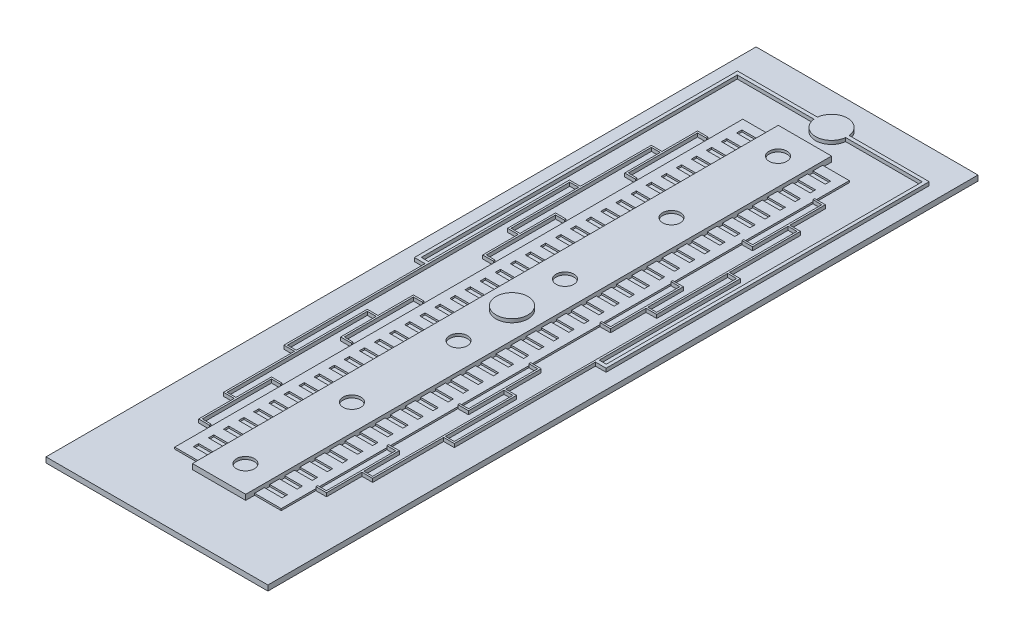
SolidWorks part; units mm, degrees
ref_plane "Front Plane" through (0, 0, 0) normal (0, 0, 1) x (1, 0, 0)
ref_plane "Top Plane" through (0, 0, 0) normal (0, 1, 0) x (1, 0, 0)
ref_plane "Right Plane" through (0, 0, 0) normal (1, 0, 0) x (0, 0, -1)
sketch "Sketch2" plane through (0, 0, 0) normal (0, 1, 0) x (1, 0, 0)
  line L1 (-6.25, 20) -> (6.25, 20)
  line L2 (-6.25, 20) -> (-6.25, -20)
  line L3 (-6.25, -20) -> (6.25, -20)
  line L4 (6.25, 20) -> (6.25, -20)
  line L5 (-6.25, 20) -> (6.25, -20) construction
  line L6 (-6.25, -20) -> (6.25, 20) construction
  point P0 (0, 0)
extrude "Boss-Extrude1" add sketch "Sketch2" along normal blind 0.3
sketch "Sketch3" plane through (0, 0.3, 0) normal (0, 1, 0) x (1, 0, 0)
  line L1 (-1.5, 16.5) -> (1.5, 16.5)
  line L2 (-1.5, 16.5) -> (-1.5, -16.5)
  line L3 (-1.5, -16.5) -> (1.5, -16.5)
  line L4 (1.5, 16.5) -> (1.5, -16.5)
  line L5 (-1.5, 16.5) -> (1.5, -16.5) construction
  line L6 (-1.5, -16.5) -> (1.5, 16.5) construction
  point P0 (0, 0)
extrude "Boss-Extrude2" add sketch "Sketch3" along normal blind 0.3
sketch "Sketch4" plane through (0, 0.3, 0) normal (0, 1, 0) x (1, 0, 0)
  line L0 (1.5, 16) -> (3, 16)
  line L1 (1.5, 16) -> (1.5, -16)
  line L2 (3, 16) -> (3, -16)
  line L3 (1.5, -16) -> (3, -16)
  line L4 (1.5, -16.5) -> (1.5, 16.5) construction
  line L5 (0, 18.1281) -> (0, -18.1281) construction
  line L6 (-3, 16) -> (-3, -16)
  line L7 (-1.5, -16) -> (-3, -16)
  line L8 (-1.5, 16) -> (-1.5, -16)
  line L9 (-1.5, 16) -> (-3, 16)
  point P11 (0, 0)
  dimension "D1" = 0.5
extrude "Boss-Extrude3" add sketch "Sketch4" along normal blind 0.1
sketch "Sketch5" plane through (0, 0.4, 0) normal (0, 1, 0) x (1, 0, 0)
  line L0 (1.5, 15.45) -> (2.5, 15.45)
  line L1 (1.5, 15.45) -> (1.5, 15.15)
  line L2 (2.5, 15.45) -> (2.5, 15.15)
  line L3 (1.5, 15.15) -> (2.5, 15.15)
  line L4 (1.5, -16.5) -> (1.5, 16.5) construction
  line L5 (-2.5, 15.45) -> (-1.5, 15.45)
  line L6 (-2.5, 15.45) -> (-2.5, 15.15)
  line L7 (-2.5, 15.15) -> (-1.5, 15.15)
  line L8 (-1.5, 15.45) -> (-1.5, 15.15)
  line L9 (-2.5, 14.6) -> (-1.5, 14.6)
  line L10 (-2.5, 14.6) -> (-2.5, 14.3)
  line L11 (-2.5, 14.3) -> (-1.5, 14.3)
  line L12 (-1.5, 14.6) -> (-1.5, 14.3)
  line L13 (-2.5, 13.75) -> (-1.5, 13.75)
  line L14 (-2.5, 13.75) -> (-2.5, 13.45)
  line L15 (-2.5, 13.45) -> (-1.5, 13.45)
  line L16 (-1.5, 13.75) -> (-1.5, 13.45)
  line L17 (-2.5, 12.9) -> (-1.5, 12.9)
  line L18 (-2.5, 12.9) -> (-2.5, 12.6)
  line L19 (-2.5, 12.6) -> (-1.5, 12.6)
  line L20 (-1.5, 12.9) -> (-1.5, 12.6)
  line L21 (-2.5, 12.05) -> (-1.5, 12.05)
  line L22 (-2.5, 12.05) -> (-2.5, 11.75)
  line L23 (-2.5, 11.75) -> (-1.5, 11.75)
  line L24 (-1.5, 12.05) -> (-1.5, 11.75)
  line L25 (-2.5, 11.2) -> (-1.5, 11.2)
  line L26 (-2.5, 11.2) -> (-2.5, 10.9)
  line L27 (-2.5, 10.9) -> (-1.5, 10.9)
  line L28 (-1.5, 11.2) -> (-1.5, 10.9)
  line L29 (-2.5, 10.35) -> (-1.5, 10.35)
  line L30 (-2.5, 10.35) -> (-2.5, 10.05)
  line L31 (-2.5, 10.05) -> (-1.5, 10.05)
  line L32 (-1.5, 10.35) -> (-1.5, 10.05)
  line L33 (-2.5, 9.5) -> (-1.5, 9.5)
  line L34 (-2.5, 9.5) -> (-2.5, 9.2)
  line L35 (-2.5, 9.2) -> (-1.5, 9.2)
  line L36 (-1.5, 9.5) -> (-1.5, 9.2)
  line L37 (-2.5, 8.65) -> (-1.5, 8.65)
  line L38 (-2.5, 8.65) -> (-2.5, 8.35)
  line L39 (-2.5, 8.35) -> (-1.5, 8.35)
  line L40 (-1.5, 8.65) -> (-1.5, 8.35)
  line L41 (-2.5, 7.8) -> (-1.5, 7.8)
  line L42 (-2.5, 7.8) -> (-2.5, 7.5)
  line L43 (-2.5, 7.5) -> (-1.5, 7.5)
  line L44 (-1.5, 7.8) -> (-1.5, 7.5)
  line L45 (-2.5, 6.95) -> (-1.5, 6.95)
  line L46 (-2.5, 6.95) -> (-2.5, 6.65)
  line L47 (-2.5, 6.65) -> (-1.5, 6.65)
  line L48 (-1.5, 6.95) -> (-1.5, 6.65)
  line L49 (-2.5, 6.1) -> (-1.5, 6.1)
  line L50 (-2.5, 6.1) -> (-2.5, 5.8)
  line L51 (-2.5, 5.8) -> (-1.5, 5.8)
  line L52 (-1.5, 6.1) -> (-1.5, 5.8)
  line L53 (-2.5, 5.25) -> (-1.5, 5.25)
  line L54 (-2.5, 5.25) -> (-2.5, 4.95)
  line L55 (-2.5, 4.95) -> (-1.5, 4.95)
  line L56 (-1.5, 5.25) -> (-1.5, 4.95)
  line L57 (-2.5, 4.4) -> (-1.5, 4.4)
  line L58 (-2.5, 4.4) -> (-2.5, 4.1)
  line L59 (-2.5, 4.1) -> (-1.5, 4.1)
  line L60 (-1.5, 4.4) -> (-1.5, 4.1)
  line L61 (-2.5, 3.55) -> (-1.5, 3.55)
  line L62 (-2.5, 3.55) -> (-2.5, 3.25)
  line L63 (-2.5, 3.25) -> (-1.5, 3.25)
  line L64 (-1.5, 3.55) -> (-1.5, 3.25)
  line L65 (-2.5, 2.7) -> (-1.5, 2.7)
  line L66 (-2.5, 2.7) -> (-2.5, 2.4)
  line L67 (-2.5, 2.4) -> (-1.5, 2.4)
  line L68 (-1.5, 2.7) -> (-1.5, 2.4)
  line L69 (-2.5, 1.85) -> (-1.5, 1.85)
  line L70 (-2.5, 1.85) -> (-2.5, 1.55)
  line L71 (-2.5, 1.55) -> (-1.5, 1.55)
  line L72 (-1.5, 1.85) -> (-1.5, 1.55)
  line L73 (-2.5, 1) -> (-1.5, 1)
  line L74 (-2.5, 1) -> (-2.5, 0.7)
  line L75 (-2.5, 0.7) -> (-1.5, 0.7)
  line L76 (-1.5, 1) -> (-1.5, 0.7)
  line L77 (-2.5, 0.15) -> (-1.5, 0.15)
  line L78 (-2.5, 0.15) -> (-2.5, -0.15)
  line L79 (-2.5, -0.15) -> (-1.5, -0.15)
  line L80 (-1.5, 0.15) -> (-1.5, -0.15)
  line L81 (-2.5, -0.7) -> (-1.5, -0.7)
  line L82 (-2.5, -0.7) -> (-2.5, -1)
  line L83 (-2.5, -1) -> (-1.5, -1)
  line L84 (-1.5, -0.7) -> (-1.5, -1)
  line L85 (-2.5, -1.55) -> (-1.5, -1.55)
  line L86 (-2.5, -1.55) -> (-2.5, -1.85)
  line L87 (-2.5, -1.85) -> (-1.5, -1.85)
  line L88 (-1.5, -1.55) -> (-1.5, -1.85)
  line L89 (-2.5, -2.4) -> (-1.5, -2.4)
  line L90 (-2.5, -2.4) -> (-2.5, -2.7)
  line L91 (-2.5, -2.7) -> (-1.5, -2.7)
  line L92 (-1.5, -2.4) -> (-1.5, -2.7)
  line L93 (-2.5, -3.25) -> (-1.5, -3.25)
  line L94 (-2.5, -3.25) -> (-2.5, -3.55)
  line L95 (-2.5, -3.55) -> (-1.5, -3.55)
  line L96 (-1.5, -3.25) -> (-1.5, -3.55)
  line L97 (-2.5, -4.1) -> (-1.5, -4.1)
  line L98 (-2.5, -4.1) -> (-2.5, -4.4)
  line L99 (-2.5, -4.4) -> (-1.5, -4.4)
  line L100 (-1.5, -4.1) -> (-1.5, -4.4)
  line L101 (-2.5, -4.95) -> (-1.5, -4.95)
  line L102 (-2.5, -4.95) -> (-2.5, -5.25)
  line L103 (-2.5, -5.25) -> (-1.5, -5.25)
  line L104 (-1.5, -4.95) -> (-1.5, -5.25)
  line L105 (-2.5, -5.8) -> (-1.5, -5.8)
  line L106 (-2.5, -5.8) -> (-2.5, -6.1)
  line L107 (-2.5, -6.1) -> (-1.5, -6.1)
  line L108 (-1.5, -5.8) -> (-1.5, -6.1)
  line L109 (-2.5, -6.65) -> (-1.5, -6.65)
  line L110 (-2.5, -6.65) -> (-2.5, -6.95)
  line L111 (-2.5, -6.95) -> (-1.5, -6.95)
  line L112 (-1.5, -6.65) -> (-1.5, -6.95)
  line L113 (-2.5, -7.5) -> (-1.5, -7.5)
  line L114 (-2.5, -7.5) -> (-2.5, -7.8)
  line L115 (-2.5, -7.8) -> (-1.5, -7.8)
  line L116 (-1.5, -7.5) -> (-1.5, -7.8)
  line L117 (-2.5, -8.35) -> (-1.5, -8.35)
  line L118 (-2.5, -8.35) -> (-2.5, -8.65)
  line L119 (-2.5, -8.65) -> (-1.5, -8.65)
  line L120 (-1.5, -8.35) -> (-1.5, -8.65)
  line L121 (-2.5, -9.2) -> (-1.5, -9.2)
  line L122 (-2.5, -9.2) -> (-2.5, -9.5)
  line L123 (-2.5, -9.5) -> (-1.5, -9.5)
  line L124 (-1.5, -9.2) -> (-1.5, -9.5)
  line L125 (-2.5, -10.05) -> (-1.5, -10.05)
  line L126 (-2.5, -10.05) -> (-2.5, -10.35)
  line L127 (-2.5, -10.35) -> (-1.5, -10.35)
  line L128 (-1.5, -10.05) -> (-1.5, -10.35)
  line L129 (-2.5, -10.9) -> (-1.5, -10.9)
  line L130 (-2.5, -10.9) -> (-2.5, -11.2)
  line L131 (-2.5, -11.2) -> (-1.5, -11.2)
  line L132 (-1.5, -10.9) -> (-1.5, -11.2)
  line L133 (-2.5, -11.75) -> (-1.5, -11.75)
  line L134 (-2.5, -11.75) -> (-2.5, -12.05)
  line L135 (-2.5, -12.05) -> (-1.5, -12.05)
  line L136 (-1.5, -11.75) -> (-1.5, -12.05)
  line L137 (-2.5, -12.6) -> (-1.5, -12.6)
  line L138 (-2.5, -12.6) -> (-2.5, -12.9)
  line L139 (-2.5, -12.9) -> (-1.5, -12.9)
  line L140 (-1.5, -12.6) -> (-1.5, -12.9)
  line L141 (-2.5, -13.45) -> (-1.5, -13.45)
  line L142 (-2.5, -13.45) -> (-2.5, -13.75)
  line L143 (-2.5, -13.75) -> (-1.5, -13.75)
  line L144 (-1.5, -13.45) -> (-1.5, -13.75)
  line L145 (-2.5, -14.3) -> (-1.5, -14.3)
  line L146 (-2.5, -14.3) -> (-2.5, -14.6)
  line L147 (-2.5, -14.6) -> (-1.5, -14.6)
  line L148 (-1.5, -14.3) -> (-1.5, -14.6)
  line L149 (-2.5, -15.15) -> (-1.5, -15.15)
  line L150 (-2.5, -15.15) -> (-2.5, -15.45)
  line L151 (-2.5, -15.45) -> (-1.5, -15.45)
  line L152 (-1.5, -15.15) -> (-1.5, -15.45)
  line L153 (1.5, 14.6) -> (2.5, 14.6)
  line L154 (1.5, 14.6) -> (1.5, 14.3)
  line L155 (1.5, 14.3) -> (2.5, 14.3)
  line L156 (2.5, 14.6) -> (2.5, 14.3)
  line L157 (1.5, 13.75) -> (2.5, 13.75)
  line L158 (1.5, 13.75) -> (1.5, 13.45)
  line L159 (1.5, 13.45) -> (2.5, 13.45)
  line L160 (2.5, 13.75) -> (2.5, 13.45)
  line L161 (1.5, 12.9) -> (2.5, 12.9)
  line L162 (1.5, 12.9) -> (1.5, 12.6)
  line L163 (1.5, 12.6) -> (2.5, 12.6)
  line L164 (2.5, 12.9) -> (2.5, 12.6)
  line L165 (1.5, 12.05) -> (2.5, 12.05)
  line L166 (1.5, 12.05) -> (1.5, 11.75)
  line L167 (1.5, 11.75) -> (2.5, 11.75)
  line L168 (2.5, 12.05) -> (2.5, 11.75)
  line L169 (1.5, 11.2) -> (2.5, 11.2)
  line L170 (1.5, 11.2) -> (1.5, 10.9)
  line L171 (1.5, 10.9) -> (2.5, 10.9)
  line L172 (2.5, 11.2) -> (2.5, 10.9)
  line L173 (1.5, 10.35) -> (2.5, 10.35)
  line L174 (1.5, 10.35) -> (1.5, 10.05)
  line L175 (1.5, 10.05) -> (2.5, 10.05)
  line L176 (2.5, 10.35) -> (2.5, 10.05)
  line L177 (1.5, 9.5) -> (2.5, 9.5)
  line L178 (1.5, 9.5) -> (1.5, 9.2)
  line L179 (1.5, 9.2) -> (2.5, 9.2)
  line L180 (2.5, 9.5) -> (2.5, 9.2)
  line L181 (1.5, 8.65) -> (2.5, 8.65)
  line L182 (1.5, 8.65) -> (1.5, 8.35)
  line L183 (1.5, 8.35) -> (2.5, 8.35)
  line L184 (2.5, 8.65) -> (2.5, 8.35)
  line L185 (1.5, 7.8) -> (2.5, 7.8)
  line L186 (1.5, 7.8) -> (1.5, 7.5)
  line L187 (1.5, 7.5) -> (2.5, 7.5)
  line L188 (2.5, 7.8) -> (2.5, 7.5)
  line L189 (1.5, 6.95) -> (2.5, 6.95)
  line L190 (1.5, 6.95) -> (1.5, 6.65)
  line L191 (1.5, 6.65) -> (2.5, 6.65)
  line L192 (2.5, 6.95) -> (2.5, 6.65)
  line L193 (1.5, 6.1) -> (2.5, 6.1)
  line L194 (1.5, 6.1) -> (1.5, 5.8)
  line L195 (1.5, 5.8) -> (2.5, 5.8)
  line L196 (2.5, 6.1) -> (2.5, 5.8)
  line L197 (1.5, 5.25) -> (2.5, 5.25)
  line L198 (1.5, 5.25) -> (1.5, 4.95)
  line L199 (1.5, 4.95) -> (2.5, 4.95)
  line L200 (2.5, 5.25) -> (2.5, 4.95)
  line L201 (1.5, 4.4) -> (2.5, 4.4)
  line L202 (1.5, 4.4) -> (1.5, 4.1)
  line L203 (1.5, 4.1) -> (2.5, 4.1)
  line L204 (2.5, 4.4) -> (2.5, 4.1)
  line L205 (1.5, 3.55) -> (2.5, 3.55)
  line L206 (1.5, 3.55) -> (1.5, 3.25)
  line L207 (1.5, 3.25) -> (2.5, 3.25)
  line L208 (2.5, 3.55) -> (2.5, 3.25)
  line L209 (1.5, 2.7) -> (2.5, 2.7)
  line L210 (1.5, 2.7) -> (1.5, 2.4)
  line L211 (1.5, 2.4) -> (2.5, 2.4)
  line L212 (2.5, 2.7) -> (2.5, 2.4)
  line L213 (1.5, 1.85) -> (2.5, 1.85)
  line L214 (1.5, 1.85) -> (1.5, 1.55)
  line L215 (1.5, 1.55) -> (2.5, 1.55)
  line L216 (2.5, 1.85) -> (2.5, 1.55)
  line L217 (1.5, 1) -> (2.5, 1)
  line L218 (1.5, 1) -> (1.5, 0.7)
  line L219 (1.5, 0.7) -> (2.5, 0.7)
  line L220 (2.5, 1) -> (2.5, 0.7)
  line L221 (1.5, 0.15) -> (2.5, 0.15)
  line L222 (1.5, 0.15) -> (1.5, -0.15)
  line L223 (1.5, -0.15) -> (2.5, -0.15)
  line L224 (2.5, 0.15) -> (2.5, -0.15)
  line L225 (1.5, -0.7) -> (2.5, -0.7)
  line L226 (1.5, -0.7) -> (1.5, -1)
  line L227 (1.5, -1) -> (2.5, -1)
  line L228 (2.5, -0.7) -> (2.5, -1)
  line L229 (1.5, -1.55) -> (2.5, -1.55)
  line L230 (1.5, -1.55) -> (1.5, -1.85)
  line L231 (1.5, -1.85) -> (2.5, -1.85)
  line L232 (2.5, -1.55) -> (2.5, -1.85)
  line L233 (1.5, -2.4) -> (2.5, -2.4)
  line L234 (1.5, -2.4) -> (1.5, -2.7)
  line L235 (1.5, -2.7) -> (2.5, -2.7)
  line L236 (2.5, -2.4) -> (2.5, -2.7)
  line L237 (1.5, -3.25) -> (2.5, -3.25)
  line L238 (1.5, -3.25) -> (1.5, -3.55)
  line L239 (1.5, -3.55) -> (2.5, -3.55)
  line L240 (2.5, -3.25) -> (2.5, -3.55)
  line L241 (1.5, -4.1) -> (2.5, -4.1)
  line L242 (1.5, -4.1) -> (1.5, -4.4)
  line L243 (1.5, -4.4) -> (2.5, -4.4)
  line L244 (2.5, -4.1) -> (2.5, -4.4)
  line L245 (1.5, -4.95) -> (2.5, -4.95)
  line L246 (1.5, -4.95) -> (1.5, -5.25)
  line L247 (1.5, -5.25) -> (2.5, -5.25)
  line L248 (2.5, -4.95) -> (2.5, -5.25)
  line L249 (1.5, -5.8) -> (2.5, -5.8)
  line L250 (1.5, -5.8) -> (1.5, -6.1)
  line L251 (1.5, -6.1) -> (2.5, -6.1)
  line L252 (2.5, -5.8) -> (2.5, -6.1)
  line L253 (1.5, -6.65) -> (2.5, -6.65)
  line L254 (1.5, -6.65) -> (1.5, -6.95)
  line L255 (1.5, -6.95) -> (2.5, -6.95)
  line L256 (2.5, -6.65) -> (2.5, -6.95)
  line L257 (1.5, -7.5) -> (2.5, -7.5)
  line L258 (1.5, -7.5) -> (1.5, -7.8)
  line L259 (1.5, -7.8) -> (2.5, -7.8)
  line L260 (2.5, -7.5) -> (2.5, -7.8)
  line L261 (1.5, -8.35) -> (2.5, -8.35)
  line L262 (1.5, -8.35) -> (1.5, -8.65)
  line L263 (1.5, -8.65) -> (2.5, -8.65)
  line L264 (2.5, -8.35) -> (2.5, -8.65)
  line L265 (1.5, -9.2) -> (2.5, -9.2)
  line L266 (1.5, -9.2) -> (1.5, -9.5)
  line L267 (1.5, -9.5) -> (2.5, -9.5)
  line L268 (2.5, -9.2) -> (2.5, -9.5)
  line L269 (1.5, -10.05) -> (2.5, -10.05)
  line L270 (1.5, -10.05) -> (1.5, -10.35)
  line L271 (1.5, -10.35) -> (2.5, -10.35)
  line L272 (2.5, -10.05) -> (2.5, -10.35)
  line L273 (1.5, -10.9) -> (2.5, -10.9)
  line L274 (1.5, -10.9) -> (1.5, -11.2)
  line L275 (1.5, -11.2) -> (2.5, -11.2)
  line L276 (2.5, -10.9) -> (2.5, -11.2)
  line L277 (1.5, -11.75) -> (2.5, -11.75)
  line L278 (1.5, -11.75) -> (1.5, -12.05)
  line L279 (1.5, -12.05) -> (2.5, -12.05)
  line L280 (2.5, -11.75) -> (2.5, -12.05)
  line L281 (1.5, -12.6) -> (2.5, -12.6)
  line L282 (1.5, -12.6) -> (1.5, -12.9)
  line L283 (1.5, -12.9) -> (2.5, -12.9)
  line L284 (2.5, -12.6) -> (2.5, -12.9)
  line L285 (1.5, -13.45) -> (2.5, -13.45)
  line L286 (1.5, -13.45) -> (1.5, -13.75)
  line L287 (1.5, -13.75) -> (2.5, -13.75)
  line L288 (2.5, -13.45) -> (2.5, -13.75)
  line L289 (1.5, -14.3) -> (2.5, -14.3)
  line L290 (1.5, -14.3) -> (1.5, -14.6)
  line L291 (1.5, -14.6) -> (2.5, -14.6)
  line L292 (2.5, -14.3) -> (2.5, -14.6)
  line L293 (1.5, -15.15) -> (2.5, -15.15)
  line L294 (1.5, -15.15) -> (1.5, -15.45)
  line L295 (1.5, -15.45) -> (2.5, -15.45)
  line L296 (2.5, -15.15) -> (2.5, -15.45)
  dimension "D1" = 0.55
  dimension "D2" = 2
  dimension "D3" = 37
extrude "Cut-Extrude1" cut sketch "Sketch5" against normal blind 0.1
sketch "Sketch6" plane through (0, 0.3, 0) normal (0, 1, 0) x (1, 0, 0)
  line L0 (-11.4943, 0) -> (11.4943, 0) construction
  line L1 (0, 19.3574) -> (0, -19.3574) construction
  line L2 (1.5, 16.5) -> (-1.5, 16.5) construction
  line L3 (-5.4, 18.1) -> (5.4, 18.1)
  line L4 (-5.2112, 17.9) -> (5.2112, 17.9)
  line L5 (-5.4, 18.1) -> (-5.4, -0.1)
  line L6 (-5.2112, 17.9) -> (-5.2112, 0.1)
  line L7 (-5.2112, 0.1) -> (-4.8112, 0.1)
  line L8 (-5.4, -0.1) -> (-4.8, -0.1)
  line L9 (-3, 16) -> (-3, -16) construction
  line L10 (-3, 16) -> (-3, -16) construction
  line L11 (-3, 14.05) -> (-3.6, 14.05)
  line L12 (-3, 13.95) -> (-3.5, 13.95)
  line L13 (-3, 9.95) -> (-3.6, 9.95)
  line L14 (-3, 10.05) -> (-3.5, 10.05)
  line L15 (-3.5, 10.05) -> (-3.5, 13.95)
  line L16 (-3.6, 14.05) -> (-3.6, 12.05)
  line L17 (-3.6, 11.95) -> (-3.6, 9.95)
  line L18 (-3, 12) -> (-3.7147, 12) construction
  line L19 (-3, 6.05) -> (-3.6, 6.05)
  line L20 (-3, 5.95) -> (-3.5, 5.95)
  line L21 (-3, 1.95) -> (-3.6, 1.95)
  line L22 (-3, 2.05) -> (-3.5, 2.05)
  line L23 (-3.5, 2.05) -> (-3.5, 5.95)
  line L24 (-3.6, 6.05) -> (-3.6, 4.05)
  line L25 (-3.6, 3.95) -> (-3.6, 1.95)
  line L26 (-3, -1.95) -> (-3.6, -1.9555)
  line L27 (-3, -2.05) -> (-3.5, -2.0545)
  line L28 (-3, -6.05) -> (-3.6, -6.05)
  line L29 (-3, -5.95) -> (-3.5, -5.95)
  line L30 (-3.5, -5.95) -> (-3.5, -2.0545)
  line L31 (-3.6, -1.9555) -> (-3.6, -3.95)
  line L32 (-3.6, -4.05) -> (-3.6, -6.05)
  line L33 (-3, -9.95) -> (-3.6, -9.95)
  line L34 (-3, -10.05) -> (-3.5, -10.05)
  line L35 (-3, -14.05) -> (-3.6, -14.05)
  line L36 (-3, -13.95) -> (-3.5, -13.95)
  line L37 (-3.5, -13.95) -> (-3.5, -10.05)
  line L38 (-3.6, -9.95) -> (-3.6, -11.95)
  line L39 (-3.6, -12.05) -> (-3.6, -14.05)
  line L40 (-3, 4) -> (-3.6713, 4) construction
  line L41 (-3, -4) -> (-3.7566, -4) construction
  line L42 (-3, -12) -> (-3.7566, -12) construction
  line L43 (-3.6, 12.05) -> (-4.2, 12.05)
  line L44 (-3.6, 11.95) -> (-4.1, 11.95)
  line L45 (-3.6, 3.95) -> (-4.2, 3.95)
  line L46 (-3.6, 4.05) -> (-4.1, 4.05)
  line L47 (-4.1, 4.05) -> (-4.1, 11.95)
  line L48 (-4.2, 12.05) -> (-4.2, 8.05)
  line L49 (-4.2, 7.95) -> (-4.2, 3.95)
  line L50 (-3.6, -3.95) -> (-4.2, -3.95)
  line L51 (-3.6, -4.05) -> (-4.1, -4.05)
  line L52 (-3.6, -12.05) -> (-4.2, -12.05)
  line L53 (-3.6, -11.95) -> (-4.1, -11.95)
  line L54 (-4.1, -11.95) -> (-4.1, -4.05)
  line L55 (-4.2, -3.95) -> (-4.2, -7.95)
  line L56 (-4.2, -8.05) -> (-4.2, -12.05)
  line L57 (-3, 8) -> (-4.2671, 8) construction
  line L58 (-3, -8) -> (-4.3452, -8) construction
  line L59 (-4.2, 8.05) -> (-4.8112, 8.05)
  line L60 (-4.2, 7.95) -> (-4.7, 7.95)
  line L61 (-4.2, -8.05) -> (-4.8, -8.05)
  line L62 (-4.2, -7.95) -> (-4.7, -7.95)
  line L63 (-4.7, -7.95) -> (-4.7, 7.95)
  line L64 (-4.8112, 8.05) -> (-4.8112, 0.1)
  line L65 (-4.8, -0.1) -> (-4.8, -8.05)
  line L66 (5.2112, 17.9) -> (5.2112, 0.1)
  line L67 (5.4, 18.1) -> (5.4, -0.1)
  line L68 (3, -14.05) -> (3.6, -14.05)
  line L69 (3, -13.95) -> (3.5, -13.95)
  line L70 (3.6, -12.05) -> (3.6, -14.05)
  line L71 (3.6, -12.05) -> (4.2, -12.05)
  line L72 (3.6, -11.95) -> (4.1, -11.95)
  line L73 (3.6, -9.95) -> (3.6, -11.95)
  line L74 (3.5, -13.95) -> (3.5, -10.05)
  line L75 (3, -10.05) -> (3.5, -10.05)
  line L76 (3, -9.95) -> (3.6, -9.95)
  line L77 (4.2, -8.05) -> (4.2, -12.05)
  line L78 (4.2, -8.05) -> (4.8, -8.05)
  line L79 (4.2, -7.95) -> (4.7, -7.95)
  line L80 (3, -6.05) -> (3.6, -6.05)
  line L81 (3, -5.95) -> (3.5, -5.95)
  line L82 (4.2, -3.95) -> (4.2, -7.95)
  line L83 (4.1, -11.95) -> (4.1, -4.05)
  line L84 (3.6, -4.05) -> (3.6, -6.05)
  line L85 (3.6, -4.05) -> (4.1, -4.05)
  line L86 (3.6, -3.95) -> (4.2, -3.95)
  line L87 (3.6, -1.9555) -> (3.6, -3.95)
  line L88 (3.5, -5.95) -> (3.5, -2.0545)
  line L89 (3, -2.05) -> (3.5, -2.0545)
  line L90 (3, -1.95) -> (3.6, -1.9555)
  line L91 (4.8, -0.1) -> (4.8, -8.05)
  line L92 (5.4, -0.1) -> (4.8, -0.1)
  line L93 (5.2112, 0.1) -> (4.8112, 0.1)
  line L94 (3, 1.95) -> (3.6, 1.95)
  line L95 (3, 2.05) -> (3.5, 2.05)
  line L96 (3.6, 3.95) -> (3.6, 1.95)
  line L97 (3.6, 3.95) -> (4.2, 3.95)
  line L98 (3.6, 4.05) -> (4.1, 4.05)
  line L99 (3.6, 6.05) -> (3.6, 4.05)
  line L100 (3.5, 2.05) -> (3.5, 5.95)
  line L101 (3, 5.95) -> (3.5, 5.95)
  line L102 (3, 6.05) -> (3.6, 6.05)
  line L103 (4.2, 7.95) -> (4.2, 3.95)
  line L104 (4.8112, 8.05) -> (4.8112, 0.1)
  line L105 (4.7, -7.95) -> (4.7, 7.95)
  line L106 (4.2, 7.95) -> (4.7, 7.95)
  line L107 (4.2, 8.05) -> (4.8112, 8.05)
  line L108 (4.1, 4.05) -> (4.1, 11.95)
  line L109 (4.2, 12.05) -> (4.2, 8.05)
  line L110 (3, 9.95) -> (3.6, 9.95)
  line L111 (3, 10.05) -> (3.5, 10.05)
  line L112 (3.6, 11.95) -> (3.6, 9.95)
  line L113 (3.6, 11.95) -> (4.1, 11.95)
  line L114 (3.6, 12.05) -> (4.2, 12.05)
  line L115 (3.5, 10.05) -> (3.5, 13.95)
  line L116 (3.6, 14.05) -> (3.6, 12.05)
  line L117 (3, 13.95) -> (3.5, 13.95)
  line L118 (3, 14.05) -> (3.6, 14.05)
  circle A0 centre (0, 18) radius 0.9
  point P0 (0, 18)
  point P3 (-3, 14.05)
  point P4 (0, 0)
  point P8 (0, 0)
  point P9 (0, 16.5)
  point P14 (0, 18.1)
  point P15 (0, 17.9)
  point P16 (-5.4, 0)
  point P19 (0, 18.1)
  point P22 (0, 17.9)
  point P24 (-5.2112, 0)
  point P28 (-3, 16)
  point P29 (-3, 13.95)
  point P31 (-3, 14)
  point P32 (-3, 12)
  point P33 (-3, 10)
  point P34 (-3, 8)
  point P35 (-3, 6)
  point P36 (-3, 4)
  point P37 (-3, 2)
  point P38 (-3, 0)
  point P39 (-3, -2)
  point P40 (-3, -4)
  point P41 (-3, -6)
  point P42 (-3, -8)
  point P43 (-3, -10)
  point P44 (-3, -12)
  point P45 (-3, -14)
  point P46 (-3, -16)
  point P55 (-3, 10.05)
  point P56 (-3, 9.95)
  point P65 (-3.6, 12)
  point P66 (-3, 6.05)
  point P67 (-3, 5.95)
  point P72 (-3, 2.05)
  point P73 (-3, 1.95)
  point P80 (-3, -1.95)
  point P81 (-3, -2.05)
  point P86 (-3, -5.95)
  point P87 (-3, -6.05)
  point P94 (-3, -9.95)
  point P95 (-3, -10.05)
  point P100 (-3, -13.95)
  point P101 (-3, -14.05)
  point P114 (-3.6, 4)
  point P115 (-3.6, -4)
  point P116 (-3.6, -12)
  point P133 (-4.2, -8)
  point P134 (-4.2, 8)
  line M35 (-3, -16) -> (-3, 16)
  line M41 (3, 16) -> (3, -16)
  dimension "D2" = 0.1
  dimension "D1" = 1.5
  dimension "D3" = 0.1
  dimension "D4" = 0.1
  dimension "D5" = 0.1
  dimension "D6" = 17
  dimension "D7" = 0.05
  dimension "D8" = 0.05
  dimension "D9" = 0.05
  dimension "D10" = 0.05
  dimension "D11" = 0.05
  dimension "D12" = 0.05
  dimension "D13" = 0.05
  dimension "D14" = 0.05
  dimension "D15" = 0.05
  dimension "D16" = 0.05
  dimension "D17" = 0.05
  dimension "D18" = 0.05
  dimension "D19" = 0.05
  dimension "D20" = 0.05
  dimension "D21" = 0.05
  dimension "D22" = 0.05
  dimension "D23" = 0.05
  dimension "D24" = 0.05
  dimension "D25" = 0.05
  dimension "D26" = 0.05
  dimension "D27" = 0.05
  dimension "D28" = 0.05
  dimension "D29" = 0.05
  dimension "D30" = 0.05
  dimension "D31" = 0.05
  dimension "D32" = 0.05
  dimension "D33" = 0.05
  dimension "D34" = 0.05
extrude "Boss-Extrude4" add sketch "Sketch6" along normal blind 0.2 contours A0 L4 L66 L93 L104 L107 L109 L114 L116 L118 L117 L115 L111 L110 L112 L113 L108 L98 L99 L102 L101 L100 L95 L94 L96 L97 L103 L106 L105 L79 L82 L86 L87 L90 L89 L88 L81 L80 L84 L85 L83 L72 L73 L76 M41 | L3 A0 | L4 A0 L3 | L4 A0 | A0 L3 L5 L8 L65 L61 L56 L52 L39 L35 L36 L37 L34 L33 L38 L53 L54 L51 L32 L28 L29 L30 L27 L26 L31 L50 L55 L62 L63 L60 L49 L45 L25 L21 L22 L23 L20 L19 L24 L46 L47 L44 L17 L13 M35 region at (-3.1472, 0.3, -18.0675) region at (0, 0.3, -18.4366) region at (0, 0.3, -18) region at (3.1472, 0.3, -18.0675) region at (0, 0.3, -17.5634)
sketch "Sketch7" plane through (0, 0.6, 0) normal (0, 1, 0) x (1, 0, 0)
  circle A0 centre (0, 0) radius 0.9
extrude "Boss-Extrude5" add sketch "Sketch7" along normal blind 0.2
sketch "Sketch8" plane through (0, 0.6, 0) normal (0, 1, 0) x (1, 0, 0)
  line L0 (0, 17.2781) -> (0, -17.2781) construction
  circle A0 centre (0, 14.9852) radius 0.5
  circle A1 centre (0, 8.9852) radius 0.5
  circle A2 centre (0, 2.9852) radius 0.5
  circle A3 centre (0, -3.0148) radius 0.5
  circle A4 centre (0, -9.0148) radius 0.5
  circle A5 centre (0, -15.0148) radius 0.5
  point P7 (0, 0)
  dimension "D1" = 6
extrude "Cut-Extrude2" cut sketch "Sketch8" against normal blind 0.15
